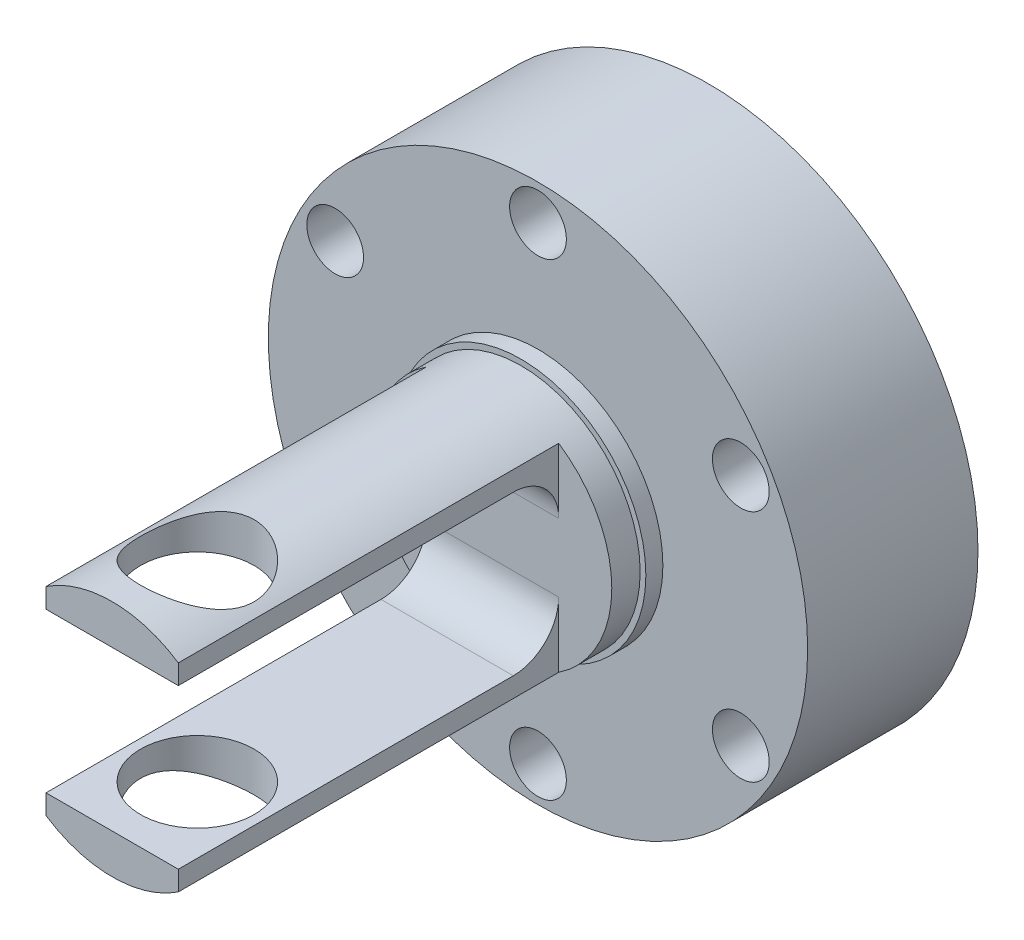
SolidWorks part; units mm, degrees
ref_plane "Płaszczyzna przednia" through (0, 0, 0) normal (0, 0, 1) x (1, 0, 0)
ref_plane "Płaszczyzna górna" through (0, 0, 0) normal (0, 1, 0) x (1, 0, 0)
ref_plane "Płaszczyzna prawa" through (0, 0, 0) normal (1, 0, 0) x (0, 0, -1)
sketch "Szkic1" plane through (0, 0, 0) normal (0, 0, 1) x (1, 0, 0)
  circle A0 centre (0, 0) radius 47.5
  dimension "D1" = 95
extrude "Dodanie-wyciągnięcie1" add sketch "Szkic1" along normal blind 30 contours A0
sketch "Szkic2" plane through (0, 0, 30) normal (0, 0, 1) x (1, 0, 0)
  circle A0 centre (0, 41.25) radius 5
  dimension "D1" = 10
  dimension "D2" = 41.25
extrude "Wytnij-wyciągnięcie1" cut sketch "Szkic2" against normal up to next
pattern_circular "Szyk kołowy1" count 6 over 360 about axis through (0, 0, 30) along (0, 0, 1) of "Wytnij-wyciągnięcie1"
sketch "Szkic3" plane through (0, 0, 30) normal (0, 0, 1) x (1, 0, 0)
  circle A0 centre (0, 0) radius 21
  dimension "D1" = 42
extrude "Dodanie-wyciągnięcie2" add sketch "Szkic3" along normal blind 0.001
sketch "Szkic4" plane through (0, 0, 30.001) normal (0, 0, 1) x (1, 0, 0)
  line L0 (-15.6525, 14) -> (15.6525, 14)
  line L1 (-15.6525, -14) -> (15.6525, -14)
  circle A1 centre (0, 0) radius 21 construction
  arc A2 (-15.6525, -14) -> (15.6525, -14) centre (0, 0) ccw
  arc A3 (15.6525, 14) -> (-15.6525, 14) centre (0, 0) ccw
  dimension "D1" = 14
  dimension "D2" = 14
extrude "Dodanie-wyciągnięcie3" add sketch "Szkic4" along normal blind 75
sketch "Szkic5" plane through (0, 0, 30.001) normal (0, 0, 1) x (1, 0, 0)
  circle A0 centre (0, 0) radius 22
  dimension "D1" = 44
extrude "Dodanie-wyciągnięcie4" add sketch "Szkic5" along normal blind 3
sketch "Szkic7" plane through (0, 0, 33.001) normal (0, 0, 1) x (1, 0, 0)
  circle A0 centre (0, 0) radius 21 construction
  circle A1 centre (0, 0) radius 21
extrude "Dodanie-wyciągnięcie5" add sketch "Szkic7" along normal blind 5
sketch "Szkic8" plane through (0, -14, 0) normal (0, 1, 0) x (1, 0, 0)
  line L0 (-15.6525, -105.001) -> (15.6525, -105.001) construction
  line L2 (15.6525, -105.001) -> (-15.6525, -105.001) construction
  circle A0 centre (0, -90.001) radius 10
  point P6 (0, -105.001)
  dimension "D1" = 20
  dimension "D2" = 15
extrude "Wytnij-wyciągnięcie2" cut sketch "Szkic8" against normal up to next and the other way through all
sketch "Szkic9" plane through (0, 0, 105.001) normal (0, 0, 1) x (1, 0, 0)
  line L0 (-11.6525, 14) -> (-11.6525, 17.4705)
  line L1 (-15.6525, 14) -> (15.6525, 14)
  line L2 (-15.6525, 14) -> (-11.6525, 14)
  line L3 (0, 16.8801) -> (0, 8.9496) construction
  line L4 (15.6525, 14) -> (11.6525, 14)
  line L5 (11.6525, 14) -> (11.6525, 17.4705)
  line L6 (0, 0) -> (11.8793, 0) construction
  line L7 (11.6525, -14) -> (11.6525, -17.4705)
  line L8 (15.6525, -14) -> (11.6525, -14)
  line L9 (-15.6525, -14) -> (-11.6525, -14)
  line L10 (-11.6525, -14) -> (-11.6525, -17.4705)
  arc A0 (11.6525, 17.4705) -> (15.6525, 14) centre (0, 0) cw
  arc A1 (15.6525, 14) -> (-15.6525, 14) centre (0, 0) ccw
  arc A2 (-11.6525, 17.4705) -> (-15.6525, 14) centre (0, 0) ccw
  arc A3 (11.6525, -17.4705) -> (15.6525, -14) centre (0, 0) ccw
  arc A4 (-11.6525, -17.4705) -> (-15.6525, -14) centre (0, 0) cw
  dimension "D2" = 4
  dimension "D1" = 0
extrude "Wytnij-wyciągnięcie3" cut sketch "Szkic9" against normal up to surface (67 mm away) up to face at (0, 0, 38.001)
fillet "Zaokrąglenie1" radius 8 2 edges at (0, -14, 38.001) (0, 14, 38.001)
